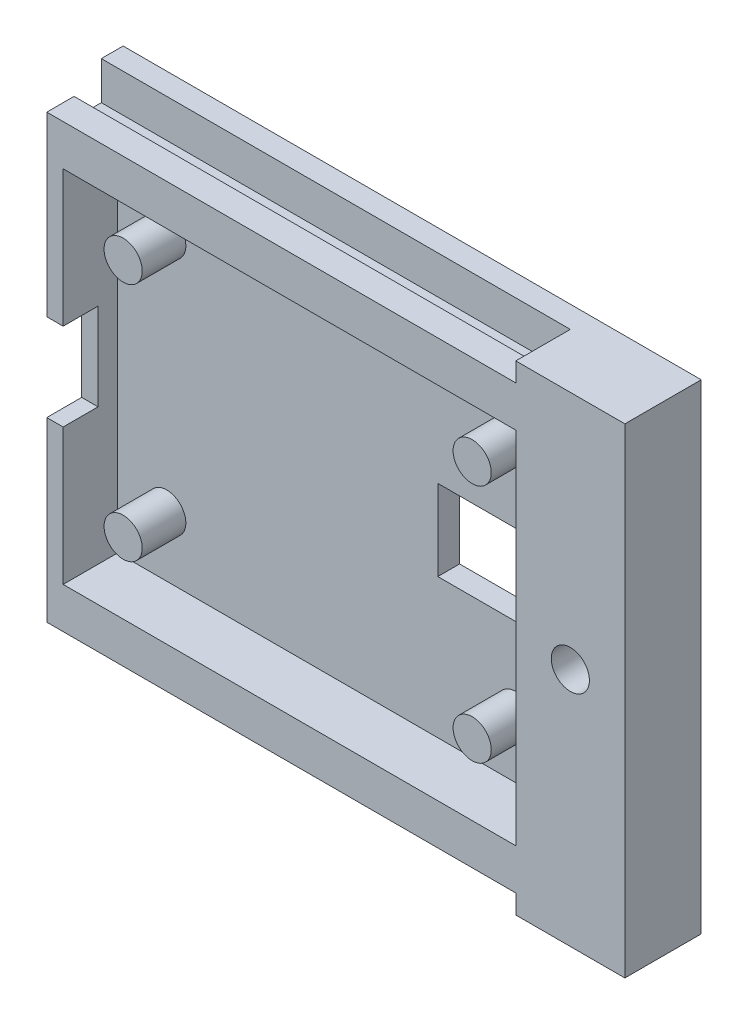
SolidWorks part; units mm, degrees
ref_plane "Alzado" through (0, 0, 0) normal (0, 0, 1) x (1, 0, 0)
ref_plane "Planta" through (0, 0, 0) normal (0, 1, 0) x (1, 0, 0)
ref_plane "Vista lateral" through (0, 0, 0) normal (1, 0, 0) x (0, 0, -1)
sketch "Croquis1" plane through (0, 0, 0) normal (0, 0, 1) x (1, 0, 0)
  line L0 (-22, 22) -> (-22, -22)
  line L1 (-22, -22) -> (31, -22)
  line L2 (31, -22) -> (31, 22)
  line L3 (31, 22) -> (-22, 22)
  line L7 (8.85, 3.7) -> (16.25, 3.7)
  line L8 (8.85, 3.7) -> (8.85, -3.7)
  line L9 (8.85, -3.7) -> (16.25, -3.7)
  line L10 (16.25, 3.7) -> (16.25, -3.7)
  line L11 (8.85, 3.7) -> (16.25, -3.7) construction
  line L12 (8.85, -3.7) -> (16.25, 3.7) construction
  line L13 (-20, 15) -> (20, 15) construction
  line L14 (-20, 15) -> (-20, -15) construction
  line L15 (-20, -15) -> (20, -15) construction
  line L16 (20, 15) -> (20, -15) construction
  line L17 (-20, 15) -> (20, -15) construction
  line L18 (-20, -15) -> (20, 15) construction
  point P0 (0, 0)
  point P3 (-22, 0)
  point P6 (12.55, 0)
  point P8 (0, 0)
  dimension "D4" = 7.4
  dimension "D1" = 44
  dimension "D2" = 2
  dimension "D3" = 7.4
  dimension "D5" = 7.45
  dimension "D6" = 40
  dimension "D7" = 30
  dimension "D8" = 11
extrude "Saliente-Extruir1" add sketch "Croquis1" along normal blind 2
sketch "Croquis4" plane through (0, 0, 2) normal (0, 0, 1) x (1, 0, 0)
  line L1 (-20, 15) -> (20, 15) construction
  line L2 (-20, 15) -> (-20, -15) construction
  line L3 (-20, -15) -> (20, -15) construction
  line L4 (20, 15) -> (20, -15) construction
  line L5 (-20, 15) -> (20, -15) construction
  line L6 (-20, -15) -> (20, 15) construction
  circle A0 centre (-16, -11) radius 1.75
  circle A1 centre (16, -11) radius 1.75
  circle A2 centre (16, 11) radius 1.75
  circle A3 centre (-16, 11) radius 1.75
  point P12 (0, 0)
  dimension "D1" = 3.5
  dimension "D2" = 30
  dimension "D3" = 40
  dimension "D4" = 4
  dimension "D5" = 4
  dimension "D6" = 4
  dimension "D7" = 4
extrude "Saliente-Extruir3" add sketch "Croquis4" along normal blind 4
sketch "Croquis5" plane through (0, 0, 0) normal (0, 0, -1) x (-1, 0, 0)
  line L0 (-31, -22) -> (-31, 22) construction
  circle A0 centre (-26, 0) radius 1.75
  point P2 (0, 0)
  dimension "D2" = 3.5
  dimension "D1" = 5
extrude "Cortar-Extruir1" cut sketch "Croquis5" against normal up to next
sketch "Croquis6" plane through (0, 0, 2) normal (0, 0, 1) x (1, 0, 0)
  line L0 (-22, -18.5) -> (21, -18.5)
  line L1 (-22, 22) -> (-22, -22) construction
  line L3 (-22, -18.5) -> (-22, 18.5)
  line L4 (-20.5, -16.5) -> (21, -16.5)
  line L7 (-20.5, 16.5) -> (21, 16.5)
  line L8 (-20.5, -16.5) -> (-20.5, 16.5)
  line L9 (21, 18.5) -> (-22, 18.5)
  line L11 (21, -18.5) -> (21, -22)
  line L12 (-22, -22) -> (31, -22) construction
  line L13 (21, -22) -> (31, -22)
  line L14 (31, -22) -> (31, 22)
  line L15 (31, 22) -> (21, 22)
  line L16 (31, 22) -> (-22, 22) construction
  line L17 (21, 22) -> (21, 18.5)
  line L18 (21, -16.5) -> (21, 16.5)
  circle A0 centre (26, 0) radius 1.75 construction
  circle A1 centre (26, 0) radius 1.75
  dimension "D1" = 37
  dimension "D2" = 2
  dimension "D3" = 2
  dimension "D4" = 18.5
  dimension "D5" = 43
  dimension "D6" = 1.5
extrude "Saliente-Extruir4" add sketch "Croquis6" along normal blind 5
sketch "Croquis7" plane through (0, 0, 7) normal (0, 0, 1) x (1, 0, 0)
  line L0 (-22, 18.5) -> (-22, 20.25)
  line L1 (-22, 22) -> (-22, 18.5) construction
  line L2 (-22, 20.25) -> (21, 20.25)
  line L3 (21, 22) -> (21, 18.5) construction
  line L4 (21, 20.25) -> (21, 18.5)
  line L5 (21, 18.5) -> (-22, 18.5)
  line L6 (-22, -18.5) -> (-22, -20.25)
  line L7 (-22, -18.5) -> (-22, -22) construction
  line L8 (-22, -20.25) -> (21, -20.25)
  line L9 (21, -18.5) -> (21, -22) construction
  line L10 (21, -20.25) -> (21, -18.5)
  line L11 (21, -18.5) -> (-22, -18.5)
extrude "Saliente-Extruir5" add sketch "Croquis7" against normal blind 2.5
sketch "Croquis8" plane through (0, 0, 7) normal (0, 0, 1) x (1, 0, 0)
  line L0 (-20.5, -4) -> (-20.5, 4)
  line L1 (-20.5, 16.5) -> (-20.5, -16.5) construction
  line L2 (-20.5, 4) -> (-22, 4)
  line L3 (-22, 20.25) -> (-22, -20.25) construction
  line L4 (-22, 4) -> (-22, -4)
  line L5 (-22, -4) -> (-20.5, -4)
  point P4 (-20.5, 0)
  dimension "D1" = 8
extrude "Cortar-Extruir3" cut sketch "Croquis8" against normal blind 3.2
sketch "Croquis9" plane through (0, 0, 0) normal (0, 0, -1) x (-1, 0, 0)
  circle A0 centre (-26, 0) radius 3.5
  dimension "D1" = 7
extrude "Cortar-Extruir4" cut sketch "Croquis9" against normal blind 3
